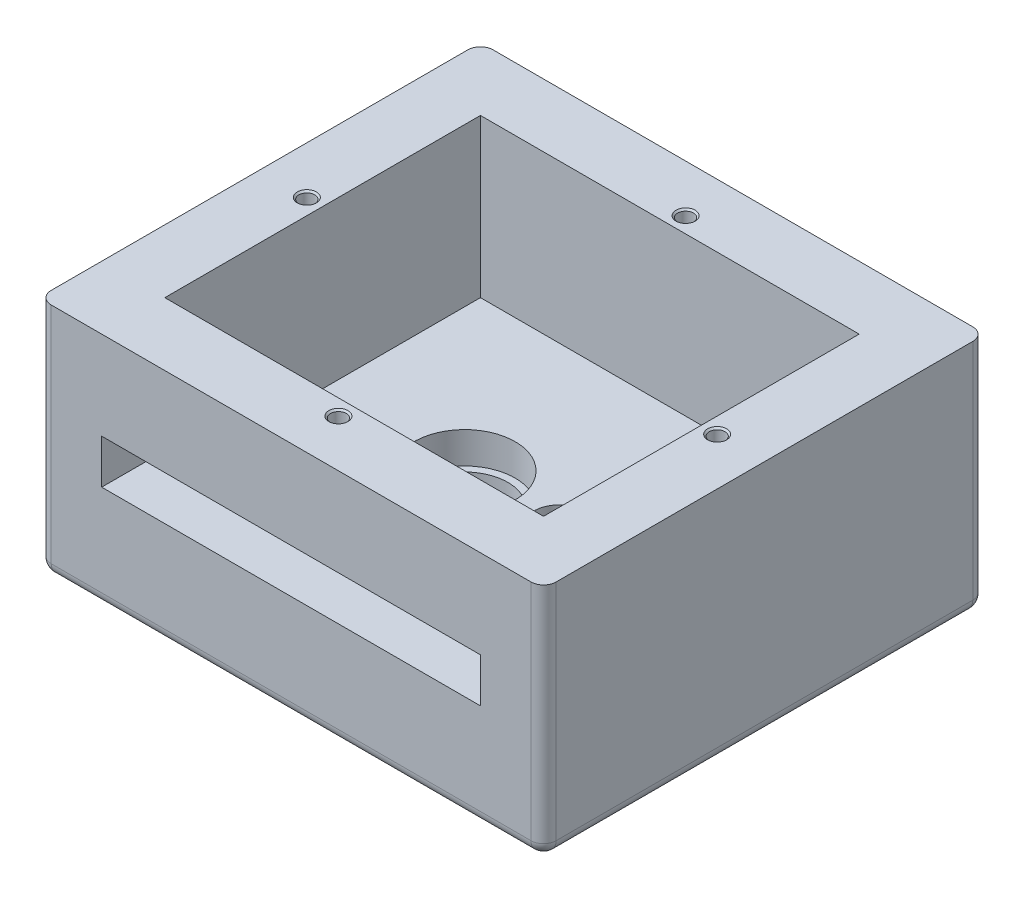
SolidWorks part; units mm, degrees
ref_plane "前视基准面" through (0, 0, 0) normal (0, 0, 1) x (1, 0, 0)
ref_plane "上视基准面" through (0, 0, 0) normal (0, 1, 0) x (1, 0, 0)
ref_plane "右视基准面" through (0, 0, 0) normal (1, 0, 0) x (0, 0, -1)
other "Configuration Table"
sketch "Box_top_view" plane through (0, 0, 0) normal (0, 1, 0) x (1, 0, 0)
  line L1 (-80, -70) -> (80, -70)
  line L2 (-80, -70) -> (-80, 70)
  line L3 (-80, 70) -> (80, 70)
  line L4 (80, -70) -> (80, 70)
  point P4 (-80, 0)
  point P6 (0, 70)
  dimension "D1" = 160
  dimension "D2" = 140
extrude "Box_extrude_part" add sketch "Box_top_view" along normal blind 70 and the other way blind 5
sketch "Scissor_crossSection" plane through (0, 0, 70) normal (0, 0, 1) x (1, 0, 0)
  line L1 (-60, 42) -> (60, 42)
  line L2 (-60, 42) -> (-60, 28)
  line L3 (-60, 28) -> (60, 28)
  line L4 (60, 42) -> (60, 28)
  line L5 (-80, -5) -> (80, -5) construction
  point P4 (0, 42)
  dimension "D1" = 14
  dimension "D2" = 120
  dimension "D3" = 33
sketch "Inner_box_cut" plane through (0, 70, 0) normal (0, 1, 0) x (1, 0, 0)
  line L1 (-60, 50) -> (60, 50)
  line L2 (-60, 50) -> (-60, -50)
  line L3 (-60, -50) -> (60, -50)
  line L4 (60, 50) -> (60, -50)
  point P5 (0, 50)
  point P7 (-60, 0)
  dimension "D1" = 120
  dimension "D2" = 100
extrude "Inner_box_cut_1" cut sketch "Inner_box_cut" against normal blind 50
extrude "Scissor_corssSection_cut" cut sketch "Scissor_crossSection" against normal blind 70
sketch "Shaft_location" plane through (0, 20, 0) normal (0, 1, 0) x (1, 0, 0)
  circle A0 centre (15, 0) radius 6
  circle A2 centre (-15, 0) radius 13.67
  dimension "D1" = 12
  dimension "D3" = 27.34
  dimension "D2" = 15
  dimension "D4" = 15
extrude "Shaft_location_cut" cut sketch "Shaft_location" against normal blind 20 contours A2 | A0
sketch "Sketch2" plane through (0, 20, 0) normal (0, 1, 0) x (1, 0, 0)
  circle A1 centre (-15, 0) radius 16
  circle A4 centre (15, 0) radius 8
  dimension "D1" = 32
  dimension "D2" = 16
  dimension "D3" = 15
  dimension "D4" = 15
extrude "Bearing_location_cut1" cut sketch "Sketch2" against normal blind 10
sketch "Hole_location" plane through (0, 70, 0) normal (0, 1, 0) x (1, 0, 0)
  line L0 (0, 30.1647) -> (0, -21.1725) construction
  line L1 (-34.0069, 0) -> (33.6799, 0) construction
  point P5 (-65, 0)
  point P6 (0, 55)
  dimension "D1" = 65
  dimension "D2" = 55
hole_wizard "M6 Tapped Hole3" positions "3DSketch3" profile "Sketch7" tap size "M6" standard "ISO"
sketch3d "3DSketch3"
  point P0 (0, 70, -55)
  point P3 (-65, 70, 0)
cosmetic thread "Hole Thread7" parameters "D1"=10, "D2"=6
cosmetic thread "Hole Thread8" parameters "D1"=10, "D2"=6
sketch "Sketch7" plane through (0, 70, -55) normal (1, 0, 0) x (0, 0, 1)
  line L0 (0, 0) -> (0, 14.5022)
  line L1 (0, 14.5022) -> (2.5, 13)
  line L2 (2.5, 13) -> (2.5, 0.525)
  line L3 (2.5, 0.525) -> (3.025, 0)
  line L5 (3.025, 0) -> (0, 0)
  line L6 (-2.5, 0.525) -> (-3.025, 0) construction
  line L10 (0, 14.5022) -> (-2.5, 13) construction
  line L11 (0, -6.35) -> (0, 107.95) construction
  dimension "Tap Drill Dia." = 5
  dimension "Tap Drill Depth" = 13
  dimension "Near C'Sink Dia." = 6.05
  dimension "Near C'Sink Angle" = 90
  dimension "Drill Angle" = 118
mirror "M6_hole_mirror" about plane through (0, 0, 0) normal (1, 0, 0) of "M6 Tapped Hole3" second plane through (0, 0, 0) second plane normal (0, 0, 1)
fillet "Edges_fillet" radius 4 8 edges at (-80, -5, 0) (0, -5, -70) (0, -5, 70) (80, -5, 0) (-80, 32.5, -70) (80, 32.5, -70) (80, 32.5, 70) (-80, 32.5, 70)
